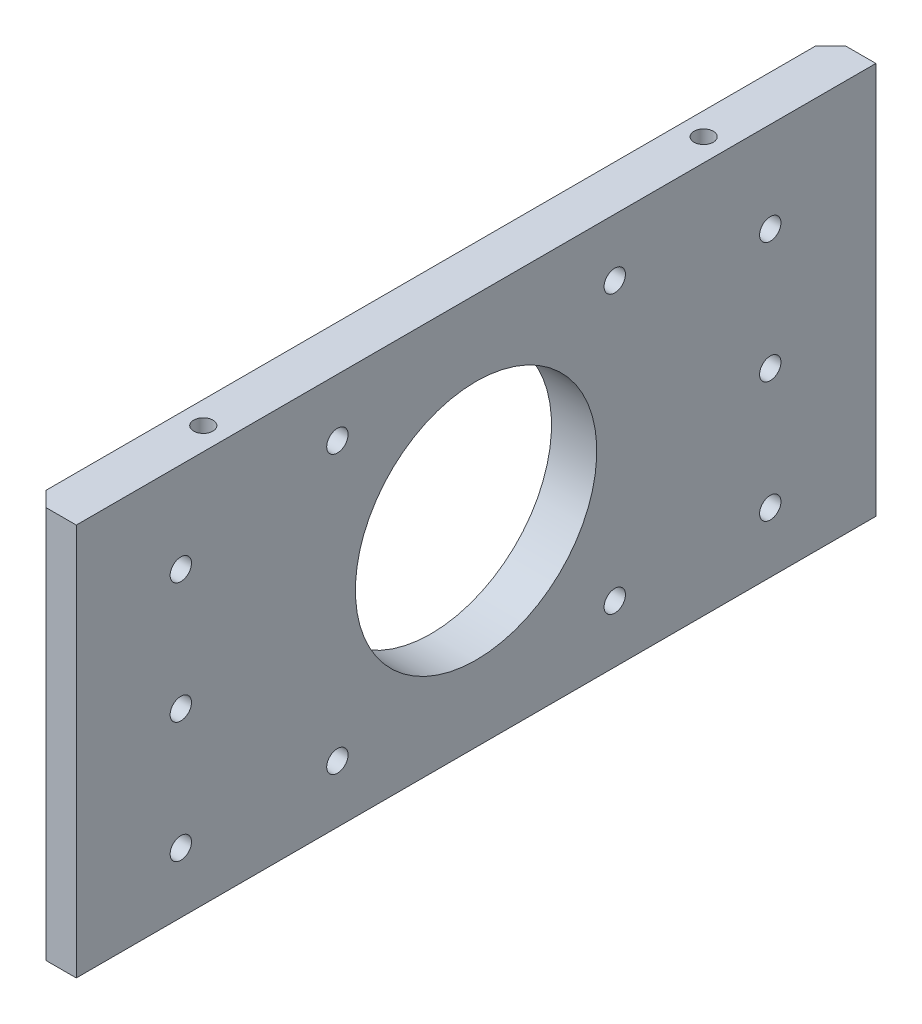
SolidWorks part; units mm, degrees
material "AISI 1015 Steel, Cold Drawn (SS)"
ref_plane "Front Plane" through (0, 0, 0) normal (0, 0, 1) x (1, 0, 0)
ref_plane "Top Plane" through (0, 0, 0) normal (0, 1, 0) x (1, 0, 0)
ref_plane "Right Plane" through (0, 0, 0) normal (1, 0, 0) x (0, 0, -1)
sketch "Sketch1" plane through (0, 0, 0) normal (0, 0, 1) x (1, 0, 0)
  line L1 (-4.7625, 41.275) -> (4.7625, 41.275)
  line L2 (-4.7625, 41.275) -> (-4.7625, -41.275)
  line L3 (-4.7625, -41.275) -> (4.7625, -41.275)
  line L4 (4.7625, 41.275) -> (4.7625, -41.275)
  line L5 (-4.7625, 41.275) -> (4.7625, -41.275) construction
  line L6 (-4.7625, -41.275) -> (4.7625, 41.275) construction
  point P0 (0, 0)
  dimension "D1" = 9.525
  dimension "D2" = 82.55
extrude "Boss-Extrude1" add sketch "Sketch1" along normal blind 168.275
hole_wizard "#8 Clearance Hole1" positions "Sketch3" profile "Sketch2" hole size "#8" standard "ANSI Inch" end condition through all
sketch "Sketch3" plane through (4.7625, 0, 0) normal (1, 0, 0) x (0, 0, -1)
  line L0 (-168.275, -41.275) -> (0, -41.275) construction
  line L1 (-168.275, -41.275) -> (-168.275, 41.275) construction
  line L2 (0, -41.275) -> (0, 41.275) construction
  point P0 (-146.278, 22.225)
  point P2 (-146.278, -3.175)
  point P4 (-146.278, -28.575)
  point P6 (-22.225, 22.225)
  point P8 (-22.225, -3.175)
  point P10 (-22.225, -28.575)
  point P17 (-168.275, 0)
  dimension "D1" = 25.4
  dimension "D2" = 25.4
  dimension "D3" = 12.7
  dimension "D4" = 22.225
  dimension "D5" = 22.225
sketch "Sketch2" plane through (4.7625, 22.225, 146.278) normal (0, 1, 0) x (0, 0, -1)
  line L0 (0, 0) -> (0, 9.525)
  line L1 (0, 9.525) -> (2.2479, 9.525)
  line L2 (2.2479, 9.525) -> (2.2479, 0)
  line L5 (2.2479, 0) -> (0, 0)
  line L11 (0, -6.35) -> (0, 107.95) construction
  dimension "Thru Hole Dia." = 4.4958
  dimension "Thru Hole Depth" = 9.525
hole_wizard "#8 Clearance Hole2" positions "Sketch4" profile "Sketch5" hole size "#8" standard "ANSI Inch" end condition through all
sketch "Sketch4" plane through (4.7625, 0, 0) normal (1, 0, 0) x (0, 0, -1)
  line L9 (-168.275, 41.275) -> (0, -41.275)
  line L10 (-84.1375, -1000) -> (-84.1375, 49000)
  line L11 (-54.9517, 29.1858) -> (-84.1375, 0)
  circle A0 centre (-84.1375, 0) radius 41.275
  point P44 (-54.9517, 29.1858)
  dimension "D1" = 82.55
  dimension "D2" = 45
sketch "Sketch5" plane through (4.7625, 29.1858, 54.9517) normal (0, 1, 0) x (0, 0, -1)
  line L0 (0, 0) -> (0, 9.525)
  line L1 (0, 9.525) -> (2.2479, 9.525)
  line L2 (2.2479, 9.525) -> (2.2479, 0)
  line L5 (2.2479, 0) -> (0, 0)
  line L11 (0, -6.35) -> (0, 107.95) construction
  dimension "Thru Hole Dia." = 4.4958
  dimension "Thru Hole Depth" = 9.525
sketch "Sketch6" plane through (4.7625, 0, 0) normal (1, 0, 0) x (0, 0, -1)
  line L0 (0, -41.275) -> (0, 41.275) construction
  line L1 (-168.275, -41.275) -> (-84.1375, 0) construction
  line L2 (-84.1375, 0) -> (0, -41.275) construction
  circle A0 centre (-84.1375, 0) radius 25.4
  point P5 (0, 0)
  dimension "D1" = 50.8
extrude "Cut-Extrude1" cut sketch "Sketch6" against normal through all
pattern_circular "CirPattern1" count 4 over 360 about axis through (-4.7625, 0, 84.1375) along (1, 0, 0) of "#8 Clearance Hole2"
chamfer "Chamfer1" distance 3.175 angle 45 2 edges at (-4.7625, 0, 0) (-4.7625, 0, 168.275)
hole_wizard "#10-32 Tapped Hole3" positions "Sketch11" profile "Sketch12" tap size "#10-32" standard "ANSI Inch"
sketch "Sketch11" plane through (79.375, 41.275, 84.1375) normal (0, 1, 0) x (1, 0, 0)
  line L0 (-52.6514, 84.1375) -> (-52.6514, 79.375) construction
  line L2 (-52.6514, 79.375) -> (-52.6514, 74.6125) construction
  line L6 (-74.6125, -52.6514) -> (-79.375, -52.6514) construction
  line L8 (-79.375, -52.6514) -> (-84.1375, -52.6514) construction
  circle A0 centre (0, 0) radius 95.25
  point P5 (-52.6514, 79.375)
  point P7 (-79.375, -52.6514)
  point P9 (-79.375, 52.6514)
  point P11 (-52.6514, -79.375)
  point P13 (52.6514, -79.375)
  point P15 (79.375, 52.6514)
  point P17 (79.375, -52.6514)
  point P19 (52.6514, 79.375)
  point P42 (0, 0)
  point P43 (0, 0)
  point P44 (0, 0)
  point P45 (0, 0)
  point P46 (0, 0)
  point P47 (0, 0)
sketch "Sketch12" plane through (26.7236, 41.275, 4.7625) normal (1, 0, 0) x (0, 0, 1)
  line L0 (0, 0) -> (0, 13.9133)
  line L1 (0, 13.9133) -> (2.0193, 12.7)
  line L2 (2.0193, 12.7) -> (2.0193, 0)
  line L3 (2.0193, 0) -> (0, 0)
  line L4 (0, 13.9133) -> (-2.0193, 12.7) construction
  line L5 (0, -6.35) -> (0, 107.95) construction
  dimension "Tap Drill Dia." = 4.0386
  dimension "Tap Drill Depth" = 12.7
  dimension "Drill Angle" = 118
cosmetic thread "Hole Thread9" parameters "D1"=0, "D2"=5.0386
cosmetic thread "Hole Thread10" parameters "D1"=0, "D2"=5.0386
hole_wizard "#10-32 Tapped Hole4" positions "Sketch13" profile "Sketch14" tap size "#10-32" standard "ANSI Inch"
sketch "Sketch13" plane through (79.375, 41.275, 84.1375) normal (0, 1, 0) x (-1, 0, 0)
  line L0 (-52.6514, 84.1375) -> (-52.6514, 79.375) construction
  line L2 (-52.6514, 79.375) -> (-52.6514, 74.6125) construction
  line L6 (-74.6125, -52.6514) -> (-79.375, -52.6514) construction
  line L8 (-79.375, -52.6514) -> (-84.1375, -52.6514) construction
  circle A0 centre (0, 0) radius 95.25
  point P5 (-52.6514, 79.375)
  point P7 (-79.375, -52.6514)
  point P9 (-79.375, 52.6514)
  point P11 (-52.6514, -79.375)
  point P13 (52.6514, -79.375)
  point P15 (79.375, 52.6514)
  point P17 (79.375, -52.6514)
  point P19 (52.6514, 79.375)
  point P42 (0, 0)
  point P43 (0, 0)
  point P44 (0, 0)
  point P45 (0, 0)
  point P46 (0, 0)
  point P47 (0, 0)
sketch "Sketch14" plane through (132.0264, 41.275, 163.5125) normal (1, 0, 0) x (0, 0, 1)
  line L0 (0, 0) -> (0, 13.9133)
  line L1 (0, 13.9133) -> (2.0193, 12.7)
  line L2 (2.0193, 12.7) -> (2.0193, 0)
  line L3 (2.0193, 0) -> (0, 0)
  line L4 (0, 13.9133) -> (-2.0193, 12.7) construction
  line L5 (0, -6.35) -> (0, 107.95) construction
  dimension "Tap Drill Dia." = 4.0386
  dimension "Tap Drill Depth" = 12.7
  dimension "Drill Angle" = 118
